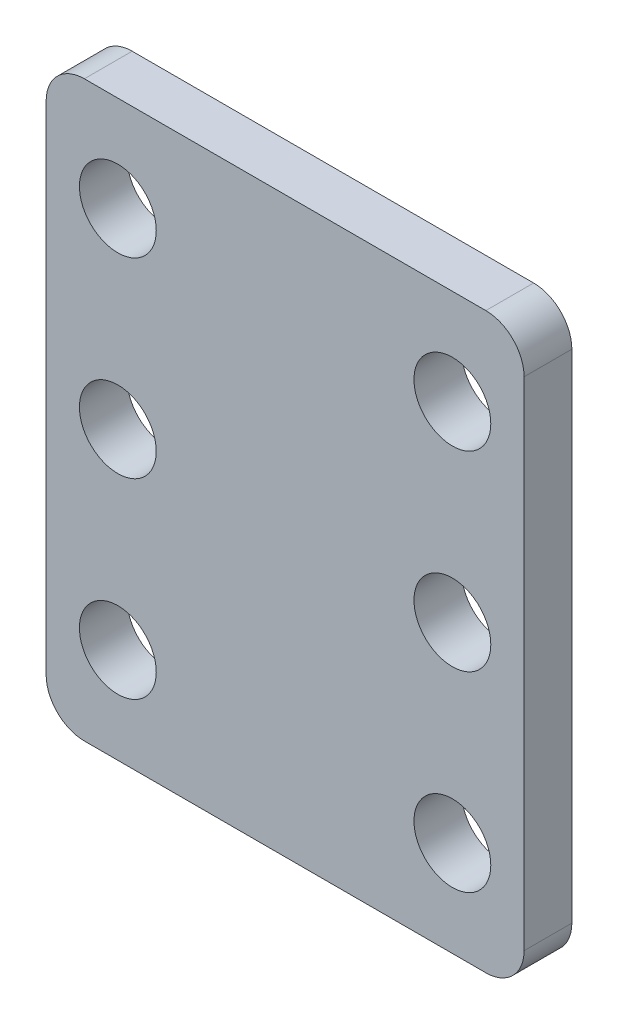
SolidWorks part; units mm, degrees
ref_plane "Front Plane" through (0, 0, 0) normal (0, 0, 1) x (1, 0, 0)
ref_plane "Top Plane" through (0, 0, 0) normal (0, 1, 0) x (1, 0, 0)
ref_plane "Right Plane" through (0, 0, 0) normal (1, 0, 0) x (0, 0, -1)
sketch "Sketch1" plane through (0, 0, 0) normal (0, 0, 1) x (1, 0, 0)
  line L1 (-15.875, -19.05) -> (15.875, -19.05)
  line L2 (-15.875, -19.05) -> (-15.875, 19.05)
  line L3 (-15.875, 19.05) -> (15.875, 19.05)
  line L4 (15.875, -19.05) -> (15.875, 19.05)
  line L5 (-15.875, -19.05) -> (15.875, 19.05) construction
  line L6 (-15.875, 19.05) -> (15.875, -19.05) construction
  line L11 (-10.5833, -12.7) -> (6.2596, 7.5116) construction
  line L13 (-11.1125, 12.7) -> (11.1125, 12.7) construction
  line L14 (-11.1125, 12.7) -> (-11.1125, -12.7) construction
  line L15 (-11.1125, -12.7) -> (11.1125, -12.7) construction
  line L16 (11.1125, 12.7) -> (11.1125, -12.7) construction
  circle A3 centre (-11.1125, 12.7) radius 2.5527
  circle A4 centre (-11.1125, 0) radius 2.5527
  circle A5 centre (11.1125, 12.7) radius 2.5527
  circle A6 centre (11.1125, -12.7) radius 2.5527
  circle A7 centre (11.1125, 0) radius 2.5527
  circle A8 centre (-11.1125, -12.7) radius 2.5527
  point P0 (0, 0)
  point P6 (0, 0)
  point P10 (-12.6848, 0)
  point P13 (0, 12.7)
  point P20 (11.1125, -12.7)
  dimension "D2" = 12.7
  dimension ".201" = 5.1054
  dimension "D4" = 12.7
  dimension "D1" = 38.1
  dimension "D3" = 31.75
  dimension "1" = 22.225
extrude "Boss-Extrude1" add sketch "Sketch1" along normal blind 3.175
fillet "Fillet1" radius 2.54 4 edges at (-15.875, 19.05, 1.5875) (-15.875, -19.05, 1.5875) (15.875, -19.05, 1.5875) (15.875, 19.05, 1.5875)
